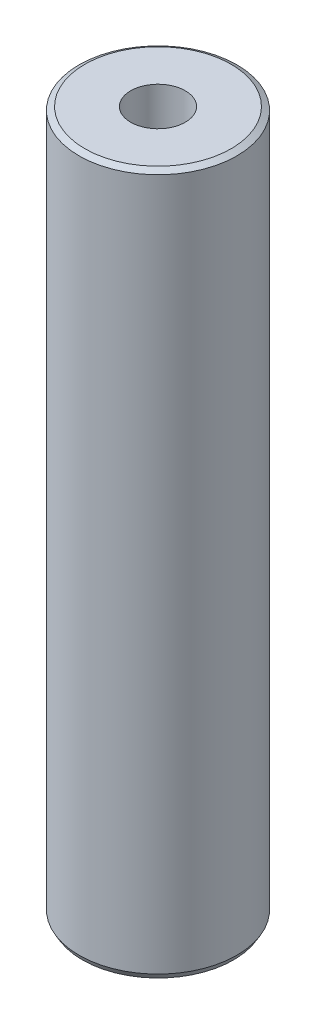
SolidWorks part; units mm, degrees
ref_plane "Front Plane" through (0, 0, 0) normal (0, 0, 1) x (1, 0, 0)
ref_plane "Top Plane" through (0, 0, 0) normal (0, 1, 0) x (1, 0, 0)
ref_plane "Right Plane" through (0, 0, 0) normal (1, 0, 0) x (0, 0, -1)
sketch "Sketch1" plane through (0, 0, 0) normal (0, 1, 0) x (1, 0, 0)
  circle A0 centre (0, 0) radius 30
  dimension "SHAFT_OD" = 60
extrude "Boss-Extrude1" add sketch "Sketch1" along normal blind 266.5824
sketch "Sketch2" plane through (0, 0, 0) normal (0, 1, 0) x (1, 0, 0)
  circle A0 centre (0, 0) radius 10.3801
  dimension "BORE_D" = 20.7602
extrude "Cut-Extrude1" cut sketch "Sketch2" along normal through all
chamfer "Chamfer1" distance 1.2617 angle 60 2 edges at (0, 266.5824, 30) (0, 0, 30) first distance on face at (0, 266.5824, 30) first distance on face at (0, 0, 10.3801)
